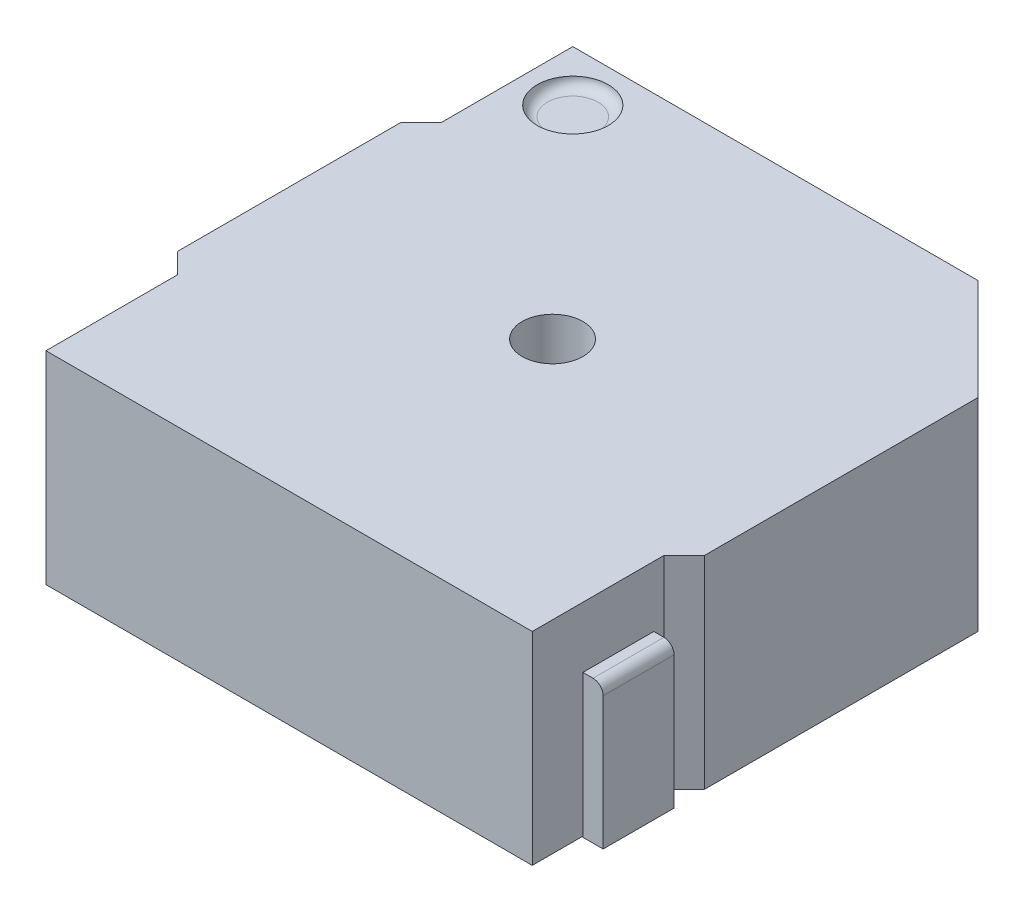
SolidWorks part; units mm, degrees
ref_plane "前视基准面" through (0, 0, 0) normal (0, 0, 1) x (1, 0, 0)
ref_plane "上视基准面" through (0, 0, 0) normal (0, 1, 0) x (1, 0, 0)
ref_plane "右视基准面" through (0, 0, 0) normal (1, 0, 0) x (0, 0, -1)
sketch "草图1" plane through (0, 0, 0) normal (0, 1, 0) x (1, 0, 0)
  line L1 (-2.6, 2.6) -> (2.6, 2.6)
  line L2 (-2.6, 2.6) -> (-2.6, -2.6)
  line L3 (-2.6, -2.6) -> (2.6, -2.6)
  line L4 (2.6, 2.6) -> (2.6, -2.6)
  line L5 (-2.6, 2.6) -> (2.6, -2.6) construction
  line L6 (-2.6, -2.6) -> (2.6, 2.6) construction
  point P0 (0, 0)
  dimension "D1" = 5.2
extrude "凸台-拉伸1" add sketch "草图1" along normal blind 2
sketch "草图2" plane through (0, 2, 0) normal (0, 1, 0) x (1, 0, 0)
  line L0 (-2.6, 0) -> (2.6, 0) construction
  line L1 (-2.6, -2.6) -> (-2.4, -2.6)
  line L2 (-2.6, -2.6) -> (-2.6, -1.1)
  line L3 (-2.6, -1.1) -> (-2.4, -1.1)
  line L4 (-2.4, -2.6) -> (-2.4, -1.1)
  line L5 (-2.6, 2.6) -> (-2.6, -2.6) construction
  line L6 (2.6, -2.6) -> (2.6, 2.6) construction
  line L7 (0, 2.6) -> (0, -2.6) construction
  line L8 (2.6, 2.6) -> (-2.6, 2.6) construction
  line L9 (-2.6, -2.6) -> (2.6, -2.6) construction
  line L10 (-2.4, 2.6) -> (-2.4, 1.1)
  line L11 (-2.6, 1.1) -> (-2.4, 1.1)
  line L12 (-2.6, 2.6) -> (-2.6, 1.1)
  line L13 (-2.6, 2.6) -> (-2.4, 2.6)
  line L14 (2.4, -2.6) -> (2.4, -1.1)
  line L15 (2.6, -1.1) -> (2.4, -1.1)
  line L16 (2.6, -2.6) -> (2.6, -1.1)
  line L17 (2.6, -2.6) -> (2.4, -2.6)
  dimension "D1" = 1.5
  dimension "D2" = 0.2
extrude "切除-拉伸1" cut sketch "草图2" against normal through all
chamfer "倒角1" distance 0.2 angle 45 3 edges at (2.4, 1, 1.1) (-2.4, 1, -1.1) (-2.4, 1, 1.1)
chamfer "倒角2" distance 1 angle 45 1 edges at (2.6, 1, -2.6)
sketch "草图3" plane through (0, 2, 0) normal (0, 1, 0) x (1, 0, 0)
  circle A0 centre (0, 0) radius 0.3
  dimension "D1" = 0.6
extrude "切除-拉伸2" cut sketch "草图3" against normal blind 1
sketch "草图4" plane through (0, 1, 0) normal (0, 1, 0) x (1, 0, 0)
  circle A0 centre (0, 0) radius 0.3
extrude "凸台-拉伸2" add sketch "草图4" along normal blind 0.1 separate body
sketch "草图5" plane through (0, 2, 0) normal (0, 1, 0) x (1, 0, 0)
  line L0 (1.6, 2.6) -> (-2.4, 2.6) construction
  line L1 (-2.4, 1.3) -> (-2.4, 2.6) construction
  circle A0 centre (-1.9, 2.1) radius 0.35
  dimension "D2" = 0.7
  dimension "D1" = 0.5
  dimension "D3" = 0.5
extrude "切除-拉伸3" cut sketch "草图5" against normal blind 0.1
fillet "圆角1" radius 0.1 1 edges at (-1.9, 1.9, -1.75)
sketch "草图6" plane through (0, 0, 0) normal (0, -1, 0) x (1, 0, 0)
  line L0 (2.6, 1.1) -> (2.6, -1.6) construction
  line L1 (2.6, 1.4) -> (1.7, 1.4)
  line L2 (2.6, 1.4) -> (2.6, 2.1)
  line L3 (2.6, 2.1) -> (1.7, 2.1)
  line L4 (1.7, 1.4) -> (1.7, 2.1)
  line L5 (-2.6, 0) -> (2.6, 0) construction
  line L6 (-2.6, -1.1) -> (-2.6, 1.1) construction
  line L7 (0, 2.6) -> (0, -2.6) construction
  line L8 (-2.4, 2.6) -> (2.4, 2.6) construction
  line L9 (1.6, -2.6) -> (-2.4, -2.6) construction
  line L10 (-1.7, 1.4) -> (-1.7, 2.1)
  line L11 (-2.6, 2.1) -> (-1.7, 2.1)
  line L12 (-2.6, 1.4) -> (-2.6, 2.1)
  line L13 (-2.6, 1.4) -> (-1.7, 1.4)
  line L14 (-2.6, -1.4) -> (-1.7, -1.4)
  line L15 (-2.6, -1.4) -> (-2.6, -2.1)
  line L16 (-2.6, -2.1) -> (-1.7, -2.1)
  line L17 (-1.7, -1.4) -> (-1.7, -2.1)
  point P17 (1.7, 1.75)
  point P22 (-1.7, 1.75)
  point P27 (-1.7, -1.75)
  dimension "D1" = 0.7
  dimension "D2" = 0.9
  dimension "D3" = 1.75
extrude "凸台-拉伸3" add sketch "草图6" against normal blind 1.4 and the other way blind 0.01 separate body
sketch "草图7" plane through (0, 0, 0) normal (0, -1, 0) x (1, 0, 0)
  line L0 (-2.6, 1.75) -> (2.6, 1.75) construction
  line L1 (-2.6, 2.1) -> (-2.6, 1.4) construction
  line L2 (2.6, 1.4) -> (2.6, 2.1) construction
  line L3 (-1.7, 1.4) -> (-1.7, 2.1) construction
  line L4 (-2.6, 0) -> (2.6, 0) construction
  line L5 (-2.6, -1.1) -> (-2.6, 1.1) construction
  line L6 (2.6, 1.1) -> (2.6, -1.6) construction
  line L7 (0, 2.6) -> (0, -2.6) construction
  line L8 (-2.4, 2.6) -> (2.4, 2.6) construction
  line L9 (1.6, -2.6) -> (-2.4, -2.6) construction
  circle A0 centre (-1.1, 1.75) radius 0.3
  circle A1 centre (-1.1, -1.75) radius 0.3
  circle A2 centre (1.1, 1.75) radius 0.3
  dimension "D1" = 0.6
  dimension "D2" = 0.6
extrude "切除-拉伸4" cut sketch "草图7" against normal blind 1
sketch "草图8" plane through (0, 1, 0) normal (0, -1, 0) x (1, 0, 0)
  circle A0 centre (1.1, 1.75) radius 0.3
  circle A1 centre (-1.1, 1.75) radius 0.3
  circle A2 centre (-1.1, -1.75) radius 0.3
extrude "凸台-拉伸4" add sketch "草图8" along normal blind 0.1 separate body
fillet "圆角2" radius 0.1 1 edges at (-2.6, 1.4, -1.75)
fillet "圆角3" radius 0.1 1 edges at (-2.6, 1.4, 1.75)
fillet "圆角4" radius 0.1 1 edges at (2.6, 1.4, 1.75)
